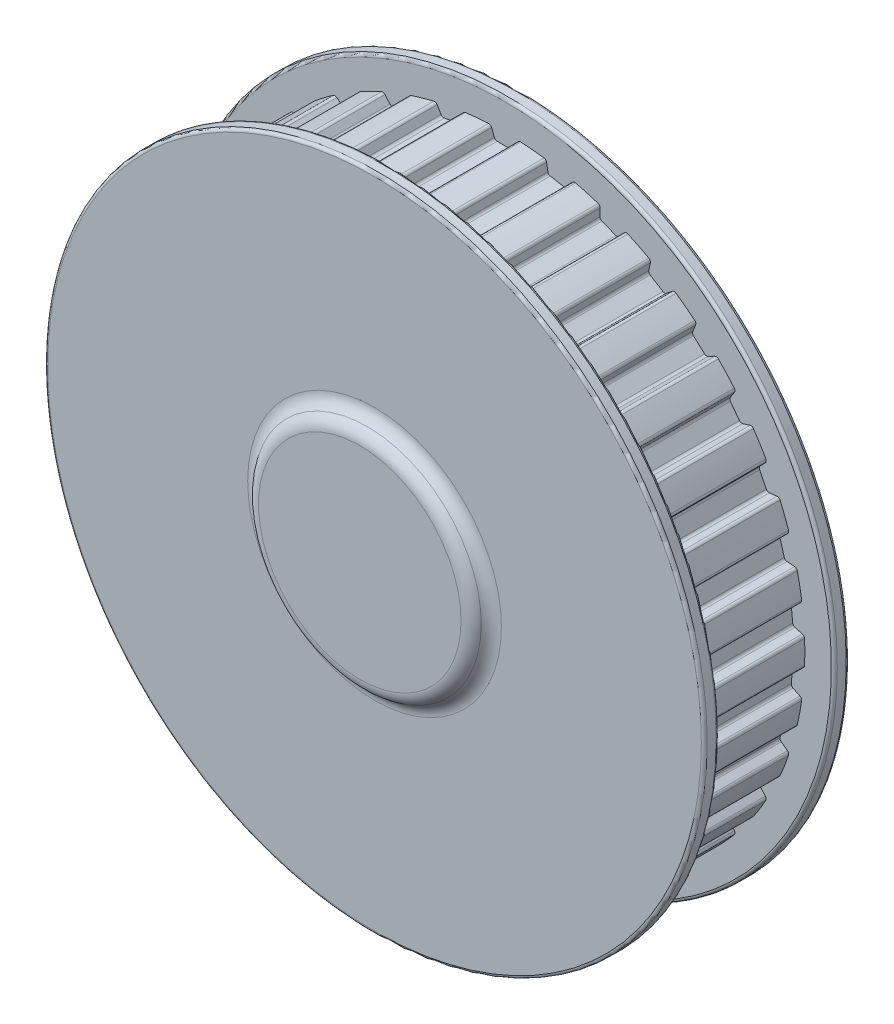
SolidWorks part; units mm, degrees
ref_plane "Front Plane" through (0, 0, 0) normal (0, 0, 1) x (1, 0, 0)
ref_plane "Top Plane" through (0, 0, 0) normal (0, 1, 0) x (1, 0, 0)
ref_plane "Right Plane" through (0, 0, 0) normal (1, 0, 0) x (0, 0, -1)
sketch "Sketch1" plane through (0, 0, 0) normal (0, 1, 0) x (1, 0, 0)
  line L0 (0, 36.1296) -> (0, -19.4741) construction
sketch "Sketch7" plane through (0, 0, 0) normal (0, 0, 1) x (1, 0, 0)
  line L0 (0, 0) -> (0, 49.7479) construction
  line L1 (-2.325, 50.7029) -> (-2.9401, 52.3929) construction
  line L2 (-2.325, 50.7029) -> (-1.6298, 48.7929) construction
  line L3 (-1.6298, 48.7929) -> (1.6298, 48.7929) construction
  line L4 (1.6298, 48.7929) -> (2.325, 50.7029) construction
  line L5 (2.325, 50.7029) -> (-2.325, 50.7029) construction
  line L6 (0, 48.7929) -> (0, 50.7029) construction
  line L7 (2.325, 50.7029) -> (2.9401, 52.3929) construction
  line L8 (-2.9401, 52.3929) -> (2.9401, 52.3929) construction
  line L9 (0, 0) -> (9.1412, 48.9008) construction
  line L10 (9.1412, 48.9008) -> (9.3264, 49.8919) construction
  line L11 (0, 50.7029) -> (0, 50.7562) construction
  line L12 (0, 50.7562) -> (0, 52.4753) construction
  line L13 (0, 51.6157) -> (9.4844, 50.7369) construction
  line L14 (9.3264, 49.8919) -> (9.6423, 51.5818) construction
  circle A1 centre (0, 0) radius 49.7479 construction
  circle A2 centre (-1.2727, 49.3029) radius 0.51 construction
  circle A3 centre (1.2727, 49.3029) radius 0.51 construction
  circle A4 centre (0, 0) radius 50.7562
  circle A5 centre (0, 0) radius 52.4753 construction
  dimension "D3" = 40
  dimension "D6" = 1.02
  dimension "D1" = 3.6
  dimension "D2" = 10.588
  dimension "D7" = 9.525
  dimension "D4" = 1.91
  dimension "D5" = 4.65
extrude "Boss-Extrude1" add sketch "Sketch7" along normal blind 7.25 and the other way blind 7.25 contours A4 region at (0, 0, 0)
sketch "Sketch14" plane through (0, 0, 0) normal (1, 0, 0) x (0, 0, -1)
  line L0 (-18, 0) -> (-18, 10)
  line L1 (-18, 0) -> (0, 0)
  line L2 (0, 0) -> (0, 19)
  line L3 (0, 19) -> (-7.25, 19)
  line L4 (-7.25, 19) -> (-18, 10)
  line L5 (-7.25, 50.7562) -> (-7.25, -50.7562) construction
  line L6 (-18, 6.7395) -> (-3.3555, 19) construction
  arc A0 (-7.25, 19) -> (-18, 10) centre (-18.1316, 21.0773) cw
  dimension "D1" = 10
  dimension "D2" = 19
  dimension "D3" = 18
  dimension "D4" = 2.5
revolve "Revolve1" add sketch "Sketch14" angle 360 about L0 region at (0, 7.5733, 7.5341) region at (0, 9.2725, 16.1663) region at (0, 17.2765, 6.6188)
sketch "Sketch9" plane through (0, 0, 0) normal (0, 0, 1) x (1, 0, 0)
  line L0 (2, 0) -> (-2, 0) construction
  line L1 (-2, 0) -> (-2, 7.5) construction
  line L2 (-2, 7.5) -> (2, 7.5) construction
  line L3 (2, 7.5) -> (2, 0) construction
  circle A0 centre (0, 0) radius 6 construction
  dimension "D1" = 12
  dimension "D2" = 4
  dimension "D3" = 7.5
sketch "Sketch10" plane through (0, 0, 0) normal (0, 0, 1) x (1, 0, 0)
  line L0 (2, 0) -> (-2, 0) construction
  line L1 (-2.2, 7.7) -> (2.2, 7.7)
  line L2 (-2.2, 7.7) -> (-2.2, 0)
  line L3 (-2.2, 0) -> (2.2, 0)
  line L4 (2.2, 7.7) -> (2.2, 0)
  line L5 (-2, 7.5) -> (2, 7.5) construction
  line L6 (2, 7.5) -> (2, 0) construction
  circle A0 centre (0, 0) radius 6.2
  circle A1 centre (0, 0) radius 6 construction
  dimension "D1" = 0.2
  dimension "D2" = 0.2
  dimension "D3" = 0.2
extrude "Cut-Extrude3" cut sketch "Sketch10" against normal through all both and the other way through all contours A0 L4 L1 L2 | L2 A0 L4 L3 | L4 A0 L2 L3 region at (0, 6.8793, 0) region at (0, 3.0348, 0) region at (0, -0.8613, 0)
sketch "Sketch11" plane through (0, 0, 0) normal (0, 1, 0) x (1, 0, 0)
  line L0 (50.7562, 7.25) -> (-50.7562, 7.25) construction
  line L1 (11, 7.25) -> (17.5, 7.25)
  line L2 (11, 7.25) -> (11, 4.75)
  line L3 (11, 4.75) -> (17.5, 4.75)
  line L4 (17.5, 7.25) -> (17.5, 4.75)
  line L5 (-50.7562, -7.25) -> (50.7562, -7.25) construction
  line L6 (11, -7.25) -> (17.5, -7.25)
  line L7 (11, -7.25) -> (11, -4.75)
  line L8 (11, -4.75) -> (17.5, -4.75)
  line L9 (17.5, -7.25) -> (17.5, -4.75)
  line L11 (11, 4.75) -> (11, -4.75) construction
  line L12 (17.5, -4.75) -> (17.5, 4.75) construction
  line L13 (6.2, 7.25) -> (-6.2, 7.25) construction
  line L14 (0, 7.25) -> (22.5, 7.25)
  line L15 (0, 7.25) -> (0, -7.25)
  line L16 (0, -7.25) -> (22.5, -7.25)
  line L17 (22.5, 7.25) -> (22.5, -7.25)
  line L18 (-6.2, -7.25) -> (6.2, -7.25) construction
  line L19 (6, 7.25) -> (6, -7.25) construction
  dimension "D1" = 22.5
  dimension "D2" = 6
  dimension "D3" = 5
  dimension "D4" = 5
  dimension "D5" = 2.5
sketch "Sketch15" plane through (0, 0, -7.25) normal (0, 0, -1) x (-1, 0, 0)
  circle A0 centre (0, 0) radius 8.0081
  circle A1 centre (0, 0) radius 2.25
  dimension "D1" = 4.5
extrude "Boss-Extrude2" add sketch "Sketch15" against normal blind 5.5
sketch "Sketch16" plane through (0, 0, -7.25) normal (0, 0, -1) x (-1, 0, 0)
  circle A0 centre (0, 0) radius 5
  dimension "D1" = 10
extrude "Cut-Extrude4" cut sketch "Sketch16" against normal blind 3
sketch "Sketch17" plane through (0, 0, -7.25) normal (0, 0, -1) x (-1, 0, 0)
  circle A0 centre (0, 0) radius 50.7562
  circle A1 centre (0, 0) radius 50.7562 construction
  circle A2 centre (0, 0) radius 5
  circle A3 centre (0, 0) radius 5 construction
extrude "Boss-Extrude3" add sketch "Sketch17" along normal blind 7.5
sketch "Sketch8" plane through (0, 0, 0) normal (0, 0, 1) x (1, 0, 0)
  line L6 (-1.6298, 48.7929) -> (-2.3444, 50.7562)
  line L7 (-2.3444, 50.7562) -> (2.3444, 50.7562)
  line L8 (2.3444, 50.7562) -> (1.6298, 48.7929)
  line L9 (1.6298, 48.7929) -> (-1.6298, 48.7929)
  line L10 (-2.325, 50.7029) -> (-1.6298, 48.7929) construction
  line L11 (1.6298, 48.7929) -> (2.325, 50.7029) construction
  line L12 (7.3636, 48.2616) -> (7.0219, 50.3227)
  line L13 (7.0219, 50.3227) -> (11.6309, 49.4612)
  line L14 (11.6309, 49.4612) -> (10.5677, 47.6626)
  line L15 (10.5677, 47.6626) -> (7.3636, 48.2616)
  line L16 (16.1063, 46.0868) -> (16.1492, 48.1756)
  line L17 (16.1492, 48.1756) -> (20.5213, 46.4818)
  line L18 (20.5213, 46.4818) -> (19.1458, 44.9093)
  line L19 (19.1458, 44.9093) -> (16.1063, 46.0868)
  line L20 (24.3004, 42.3425) -> (24.7264, 44.3879)
  line L21 (24.7264, 44.3879) -> (28.7129, 41.9196)
  line L22 (28.7129, 41.9196) -> (27.0718, 40.6266)
  line L23 (27.0718, 40.6266) -> (24.3004, 42.3425)
  line L24 (31.6671, 37.1564) -> (32.4617, 39.0887)
  line L25 (32.4617, 39.0887) -> (35.9267, 35.9299)
  line L26 (35.9267, 35.9299) -> (34.076, 34.9604)
  line L27 (34.076, 34.9604) -> (31.6671, 37.1564)
  line L28 (37.9554, 30.7049) -> (39.0915, 32.4583)
  line L29 (39.0915, 32.4583) -> (41.9171, 28.7166)
  line L30 (41.9171, 28.7166) -> (39.9198, 28.1037)
  line L31 (39.9198, 28.1037) -> (37.9554, 30.7049)
  line L32 (42.9511, 23.2078) -> (44.3901, 24.7226)
  line L33 (44.3901, 24.7226) -> (46.48, 20.5254)
  line L34 (46.48, 20.5254) -> (44.4041, 20.2899)
  line L35 (44.4041, 20.2899) -> (42.9511, 23.2078)
  line L36 (46.4842, 14.9204) -> (48.177, 16.145)
  line L37 (48.177, 16.145) -> (49.4602, 11.6352)
  line L38 (49.4602, 11.6352) -> (47.3763, 11.7852)
  line L39 (47.3763, 11.7852) -> (46.4842, 14.9204)
  line L40 (48.4344, 6.1249) -> (50.3233, 7.0176)
  line L41 (50.3233, 7.0176) -> (50.756, 2.3488)
  line L42 (50.756, 2.3488) -> (48.7351, 2.8792)
  line L43 (48.7351, 2.8792) -> (48.4344, 6.1249)
  line L44 (48.7351, -2.8792) -> (50.756, -2.3488)
  line L45 (50.756, -2.3488) -> (50.3233, -7.0176)
  line L46 (50.3233, -7.0176) -> (48.4344, -6.1249)
  line L47 (48.4344, -6.1249) -> (48.7351, -2.8792)
  line L48 (47.3763, -11.7852) -> (49.4602, -11.6352)
  line L49 (49.4602, -11.6352) -> (48.177, -16.145)
  line L50 (48.177, -16.145) -> (46.4842, -14.9204)
  line L51 (46.4842, -14.9204) -> (47.3763, -11.7852)
  line L52 (44.4041, -20.2899) -> (46.48, -20.5254)
  line L53 (46.48, -20.5254) -> (44.3901, -24.7226)
  line L54 (44.3901, -24.7226) -> (42.9511, -23.2078)
  line L55 (42.9511, -23.2078) -> (44.4041, -20.2899)
  line L56 (39.9198, -28.1037) -> (41.9171, -28.7166)
  line L57 (41.9171, -28.7166) -> (39.0915, -32.4583)
  line L58 (39.0915, -32.4583) -> (37.9554, -30.7049)
  line L59 (37.9554, -30.7049) -> (39.9198, -28.1037)
  line L60 (34.076, -34.9604) -> (35.9267, -35.9299)
  line L61 (35.9267, -35.9299) -> (32.4617, -39.0887)
  line L62 (32.4617, -39.0887) -> (31.6671, -37.1564)
  line L63 (31.6671, -37.1564) -> (34.076, -34.9604)
  line L64 (27.0718, -40.6266) -> (28.7129, -41.9196)
  line L65 (28.7129, -41.9196) -> (24.7264, -44.3879)
  line L66 (24.7264, -44.3879) -> (24.3004, -42.3425)
  line L67 (24.3004, -42.3425) -> (27.0718, -40.6266)
  line L68 (19.1458, -44.9093) -> (20.5213, -46.4818)
  line L69 (20.5213, -46.4818) -> (16.1492, -48.1756)
  line L70 (16.1492, -48.1756) -> (16.1063, -46.0868)
  line L71 (16.1063, -46.0868) -> (19.1458, -44.9093)
  line L72 (10.5677, -47.6626) -> (11.6309, -49.4612)
  line L73 (11.6309, -49.4612) -> (7.0219, -50.3227)
  line L74 (7.0219, -50.3227) -> (7.3636, -48.2616)
  line L75 (7.3636, -48.2616) -> (10.5677, -47.6626)
  line L76 (1.6298, -48.7929) -> (2.3444, -50.7562)
  line L77 (2.3444, -50.7562) -> (-2.3444, -50.7562)
  line L78 (-2.3444, -50.7562) -> (-1.6298, -48.7929)
  line L79 (-1.6298, -48.7929) -> (1.6298, -48.7929)
  line L80 (-7.3636, -48.2616) -> (-7.0219, -50.3227)
  line L81 (-7.0219, -50.3227) -> (-11.6309, -49.4612)
  line L82 (-11.6309, -49.4612) -> (-10.5677, -47.6626)
  line L83 (-10.5677, -47.6626) -> (-7.3636, -48.2616)
  line L84 (-16.1063, -46.0868) -> (-16.1492, -48.1756)
  line L85 (-16.1492, -48.1756) -> (-20.5213, -46.4818)
  line L86 (-20.5213, -46.4818) -> (-19.1458, -44.9093)
  line L87 (-19.1458, -44.9093) -> (-16.1063, -46.0868)
  line L88 (-24.3004, -42.3425) -> (-24.7264, -44.3879)
  line L89 (-24.7264, -44.3879) -> (-28.7129, -41.9196)
  line L90 (-28.7129, -41.9196) -> (-27.0718, -40.6266)
  line L91 (-27.0718, -40.6266) -> (-24.3004, -42.3425)
  line L92 (-31.6671, -37.1564) -> (-32.4617, -39.0887)
  line L93 (-32.4617, -39.0887) -> (-35.9267, -35.9299)
  line L94 (-35.9267, -35.9299) -> (-34.076, -34.9604)
  line L95 (-34.076, -34.9604) -> (-31.6671, -37.1564)
  line L96 (-37.9554, -30.7049) -> (-39.0915, -32.4583)
  line L97 (-39.0915, -32.4583) -> (-41.9171, -28.7166)
  line L98 (-41.9171, -28.7166) -> (-39.9198, -28.1037)
  line L99 (-39.9198, -28.1037) -> (-37.9554, -30.7049)
  line L100 (-42.9511, -23.2078) -> (-44.3901, -24.7226)
  line L101 (-44.3901, -24.7226) -> (-46.48, -20.5254)
  line L102 (-46.48, -20.5254) -> (-44.4041, -20.2899)
  line L103 (-44.4041, -20.2899) -> (-42.9511, -23.2078)
  line L104 (-46.4842, -14.9204) -> (-48.177, -16.145)
  line L105 (-48.177, -16.145) -> (-49.4602, -11.6352)
  line L106 (-49.4602, -11.6352) -> (-47.3763, -11.7852)
  line L107 (-47.3763, -11.7852) -> (-46.4842, -14.9204)
  line L108 (-48.4344, -6.1249) -> (-50.3233, -7.0176)
  line L109 (-50.3233, -7.0176) -> (-50.756, -2.3488)
  line L110 (-50.756, -2.3488) -> (-48.7351, -2.8792)
  line L111 (-48.7351, -2.8792) -> (-48.4344, -6.1249)
  line L112 (-48.7351, 2.8792) -> (-50.756, 2.3488)
  line L113 (-50.756, 2.3488) -> (-50.3233, 7.0176)
  line L114 (-50.3233, 7.0176) -> (-48.4344, 6.1249)
  line L115 (-48.4344, 6.1249) -> (-48.7351, 2.8792)
  line L116 (-47.3763, 11.7852) -> (-49.4602, 11.6352)
  line L117 (-49.4602, 11.6352) -> (-48.177, 16.145)
  line L118 (-48.177, 16.145) -> (-46.4842, 14.9204)
  line L119 (-46.4842, 14.9204) -> (-47.3763, 11.7852)
  line L120 (-44.4041, 20.2899) -> (-46.48, 20.5254)
  line L121 (-46.48, 20.5254) -> (-44.3901, 24.7226)
  line L122 (-44.3901, 24.7226) -> (-42.9511, 23.2078)
  line L123 (-42.9511, 23.2078) -> (-44.4041, 20.2899)
  line L124 (-39.9198, 28.1037) -> (-41.9171, 28.7166)
  line L125 (-41.9171, 28.7166) -> (-39.0915, 32.4583)
  line L126 (-39.0915, 32.4583) -> (-37.9554, 30.7049)
  line L127 (-37.9554, 30.7049) -> (-39.9198, 28.1037)
  line L128 (-34.076, 34.9604) -> (-35.9267, 35.9299)
  line L129 (-35.9267, 35.9299) -> (-32.4617, 39.0887)
  line L130 (-32.4617, 39.0887) -> (-31.6671, 37.1564)
  line L131 (-31.6671, 37.1564) -> (-34.076, 34.9604)
  line L132 (-27.0718, 40.6266) -> (-28.7129, 41.9196)
  line L133 (-28.7129, 41.9196) -> (-24.7264, 44.3879)
  line L134 (-24.7264, 44.3879) -> (-24.3004, 42.3425)
  line L135 (-24.3004, 42.3425) -> (-27.0718, 40.6266)
  line L136 (-19.1458, 44.9093) -> (-20.5213, 46.4818)
  line L137 (-20.5213, 46.4818) -> (-16.1492, 48.1756)
  line L138 (-16.1492, 48.1756) -> (-16.1063, 46.0868)
  line L139 (-16.1063, 46.0868) -> (-19.1458, 44.9093)
  line L140 (-10.5677, 47.6626) -> (-11.6309, 49.4612)
  line L141 (-11.6309, 49.4612) -> (-7.0219, 50.3227)
  line L142 (-7.0219, 50.3227) -> (-7.3636, 48.2616)
  line L143 (-7.3636, 48.2616) -> (-10.5677, 47.6626)
  circle A0 centre (0, 0) radius 50.7562 construction
  point P119 (0, 0)
  dimension "D1" = 34
extrude "Cut-Extrude2" cut sketch "Sketch8" against normal through all both and the other way through all
fillet "Fillet2" radius 0.51 136 edges at (24.7149, -44.3324, -3.75) (28.6684, -41.8845, -3.75) (32.4401, -39.0362, -3.75) (35.8765, -35.9035, -3.75) (39.0607, -32.4107, -3.75) (41.8629, -28.6999, -3.75) (44.351, -24.6815, -3.75) (46.4237, -20.519, -3.75) (48.1311, -16.1117, -3.75) (49.4036, -11.6393, -3.75) (50.2721, -6.9934, -3.75) (50.7011, -2.3632, -3.75) (50.7011, 2.3632, -3.75) (50.2721, 6.9934, -3.75) (49.4036, 11.6393, -3.75) (48.1311, 16.1117, -3.75) (46.4237, 20.519, -3.75) (44.351, 24.6815, -3.75) (41.8629, 28.6999, -3.75) (39.0607, 32.4107, -3.75) (35.8765, 35.9035, -3.75) (32.4401, 39.0362, -3.75) (28.6684, 41.8845, -3.75) (24.7149, 44.3324, -3.75) (20.484, 46.4391, -3.75) (16.148, 48.1189, -3.75) (11.602, 49.4124, -3.75) (7.0312, 50.2668, -3.75) (2.325, 50.7029, -3.75) (24.3004, -42.3425, -3.75) (27.0718, -40.6266, -3.75) (31.6671, -37.1564, -3.75) (34.076, -34.9604, -3.75) (37.9554, -30.7049, -3.75) (39.9198, -28.1037, -3.75) (42.9511, -23.2078, -3.75) (44.4041, -20.2899, -3.75) (46.4842, -14.9204, -3.75) (47.3763, -11.7852, -3.75) (48.4344, -6.1249, -3.75) (48.7351, -2.8792, -3.75) (48.7351, 2.8792, -3.75) (48.4344, 6.1249, -3.75) (47.3763, 11.7852, -3.75) (46.4842, 14.9204, -3.75) (44.4041, 20.2899, -3.75) (42.9511, 23.2078, -3.75) (39.9198, 28.1037, -3.75) (37.9554, 30.7049, -3.75) (34.076, 34.9604, -3.75) (31.6671, 37.1564, -3.75) (27.0718, 40.6266, -3.75) (24.3004, 42.3425, -3.75) (19.1458, 44.9093, -3.75) (16.1063, 46.0868, -3.75) (10.5677, 47.6626, -3.75) (7.3636, 48.2616, -3.75) (1.6298, 48.7929, -3.75) (-1.6298, 48.7929, -3.75) (-2.325, 50.7029, -3.75) (-20.484, -46.4391, -3.75) (-19.1458, -44.9093, -3.75) (-16.1063, -46.0868, -3.75) (-16.148, -48.1189, -3.75) (-11.602, -49.4124, -3.75) (-10.5677, -47.6626, -3.75) (-7.3636, -48.2616, -3.75) (-7.0312, -50.2668, -3.75) (-2.325, -50.7029, -3.75) (-1.6298, -48.7929, -3.75) (1.6298, -48.7929, -3.75) (2.325, -50.7029, -3.75) (7.0312, -50.2668, -3.75) (7.3636, -48.2616, -3.75) (10.5677, -47.6626, -3.75) (11.602, -49.4124, -3.75) (16.148, -48.1189, -3.75) (16.1063, -46.0868, -3.75) (19.1458, -44.9093, -3.75) (20.484, -46.4391, -3.75) (-24.7149, -44.3324, -3.75) (-24.3004, -42.3425, -3.75) (-27.0718, -40.6266, -3.75) (-28.6684, -41.8845, -3.75) (-32.4401, -39.0362, -3.75) (-31.6671, -37.1564, -3.75) (-34.076, -34.9604, -3.75) (-35.8765, -35.9035, -3.75) (-39.0607, -32.4107, -3.75) (-37.9554, -30.7049, -3.75) (-39.9198, -28.1037, -3.75) (-41.8629, -28.6999, -3.75) (-44.351, -24.6815, -3.75) (-42.9511, -23.2078, -3.75) (-44.4041, -20.2899, -3.75) (-46.4237, -20.519, -3.75) (-19.1458, 44.9093, -3.75) (-16.1063, 46.0868, -3.75) (-16.148, 48.1189, -3.75) (-11.602, 49.4124, -3.75) (-10.5677, 47.6626, -3.75) (-7.3636, 48.2616, -3.75) (-7.0312, 50.2668, -3.75) (-48.1311, -16.1117, -3.75) (-46.4842, -14.9204, -3.75) (-47.3763, -11.7852, -3.75) (-49.4036, -11.6393, -3.75) (-50.2721, -6.9934, -3.75) (-48.4344, -6.1249, -3.75) (-48.7351, -2.8792, -3.75) (-50.7011, -2.3632, -3.75) (-50.7011, 2.3632, -3.75) (-48.7351, 2.8792, -3.75) (-48.4344, 6.1249, -3.75) (-50.2721, 6.9934, -3.75) (-49.4036, 11.6393, -3.75) (-47.3763, 11.7852, -3.75) (-46.4842, 14.9204, -3.75) (-48.1311, 16.1117, -3.75) (-46.4237, 20.519, -3.75) (-44.4041, 20.2899, -3.75) (-42.9511, 23.2078, -3.75) (-44.351, 24.6815, -3.75) (-41.8629, 28.6999, -3.75) (-39.9198, 28.1037, -3.75) (-37.9554, 30.7049, -3.75) (-39.0607, 32.4107, -3.75) (-35.8765, 35.9035, -3.75) (-34.076, 34.9604, -3.75) (-31.6671, 37.1564, -3.75) (-32.4401, 39.0362, -3.75) (-28.6684, 41.8845, -3.75) (-27.0718, 40.6266, -3.75) (-24.3004, 42.3425, -3.75) (-24.7149, 44.3324, -3.75) (-20.484, 46.4391, -3.75)
sketch "Sketch18" plane through (0, 0, -14.75) normal (0, 0, -1) x (-1, 0, 0)
  circle A0 centre (0, 0) radius 5
  circle A1 centre (0, 0) radius 55.7562
  circle A2 centre (0, 0) radius 50.7562
  circle A3 centre (0, 0) radius 5 construction
  circle A4 centre (0, 0) radius 50.7562 construction
  dimension "D1" = 5
extrude "Boss-Extrude4" add sketch "Sketch18" along normal blind 2.5 contours A1 A2 | A2 A0 region at (54.1791, 0, -14.75) region at (49.3206, 0, -14.75)
sketch "Sketch19" plane through (0, 0, 7.25) normal (0, 0, 1) x (1, 0, 0)
  circle A0 centre (0, 0) radius 19
  circle A1 centre (0, 0) radius 55.7562
  circle A2 centre (0, 0) radius 55.7562 construction
  circle A3 centre (0, 0) radius 19 construction
extrude "Boss-Extrude5" add sketch "Sketch19" against normal blind 2.5
sketch "Sketch20" plane through (0, 0, 18) normal (0, 0, 1) x (1, 0, 0)
  line L0 (-2.2, 5.7966) -> (-2.2, 7.7)
  line L1 (-2.2, 7.7) -> (2.2, 7.7)
  line L2 (-2.2, 7.7) -> (2.2, 7.7) construction
  line L3 (2.2, 7.7) -> (2.2, 5.7966)
  circle A0 centre (0, 0) radius 6.2
  arc A1 (-2.2, 5.7966) -> (2.2, 5.7966) centre (0, 0) ccw construction
  arc M2 (2.2, 5.7966) -> (-2.2, 5.7966) centre (0, 0) cw
  line M3 (-2.2, 5.7966) -> (-2.2, 7.7)
  line M4 (-2.2, 7.7) -> (2.2, 7.7)
  line M5 (2.2, 7.7) -> (2.2, 5.7966)
extrude "Cut-Extrude5" cut sketch "Sketch20" against normal through all contours A0 M5 M4 M3 | A0 M2 region at (0, 6.8793, 18) region at (0, 0, 18)
fillet "Fillet3" radius 0.5 12 edges at (2.2, 5.7966, 0.375) (-2.2, 5.7966, 0.375) (2.2, 6.7483, 18) (-2.2, 6.7483, 18) (0, 7.7, 18) (-19, 0, 7.25) (-10, 0, 18) (0, -6.2, 18) (55.7562, 0, 4.75) (-55.7562, 0, -14.75) (-55.7562, 0, -17.25) (55.7562, 0, 7.25)
sketch "Sketch21" plane through (0, 0, 0) normal (0, 0, 1) x (1, 0, 0)
  circle A0 centre (0, 0) radius 12.5
  dimension "D1" = 25
extrude "Cut-Extrude6" cut sketch "Sketch21" against normal through all both and the other way through all
sketch "Sketch22" plane through (0, 0, 7.25) normal (0, 0, 1) x (1, 0, 0)
  circle A0 centre (0, 0) radius 18.9519
extrude "Cut-Extrude7" cut sketch "Sketch22" along normal through all
extrude "Boss-Extrude6" add sketch "Sketch22<2>" along normal blind 2.5
sketch "Sketch22<2>" plane through (0, 0, 7.25) normal (0, 0, 1) x (1, 0, 0) same geometry as "Sketch22"
fillet "Fillet4" radius 2.5 1 edges at (18.9519, 0, 7.2593)
fillet "Fillet5" radius 2.5 1 edges at (18.9519, 0, 9.75)
